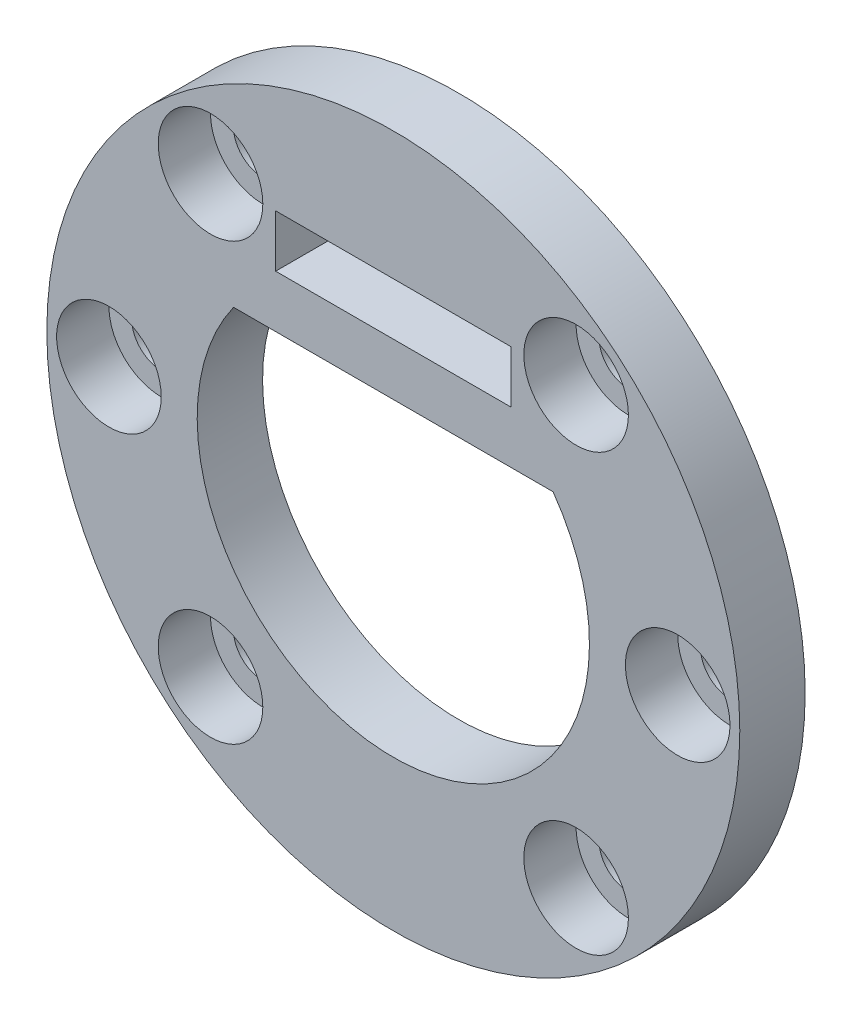
SolidWorks part; units mm, degrees
ref_plane "前视基准面" through (0, 0, 0) normal (0, 0, 1) x (1, 0, 0)
ref_plane "上视基准面" through (0, 0, 0) normal (0, 1, 0) x (1, 0, 0)
ref_plane "右视基准面" through (0, 0, 0) normal (1, 0, 0) x (0, 0, -1)
sketch "草图1" plane through (0, 0, 0) normal (0, 0, 1) x (1, 0, 0)
  circle A3 centre (0, 0) radius 26.5
extrude "凸台-拉伸1" add sketch "草图1" along normal blind 5
hole_wizard "M4 六角凹头盖的柱孔1" positions "3D草图2" profile "草图3" counterbore size "M4" standard "BSI" end condition through all
sketch3d "3D草图2"
  point P14 (-13.9806, 16.6615, 0)
  point P34 (-13.9806, 16.6615, 5)
  point P36 (13.9806, 16.6615, 5)
  point P38 (-21.75, 0, 5)
  point P40 (-13.9806, -16.6615, 5)
  point P42 (13.9806, -16.6615, 5)
  point P44 (21.75, 0, 5)
sketch "草图3" plane through (21.75, 0, 5) normal (1, 0, 0) x (0, -1, 0)
  line L0 (0, 0) -> (0, 5)
  line L1 (0, 5) -> (2.25, 5)
  line L3 (2.25, 5) -> (2.25, 4)
  line L4 (2.25, 4) -> (4, 4)
  line L5 (4, 4) -> (4, 0)
  line L7 (4, 0) -> (0, 0)
  line L11 (0, -6.35) -> (0, 107.95) construction
  dimension "通孔孔直径" = 4.5
  dimension "通孔孔深度" = 5
  dimension "柱形沉头孔直径" = 8
  dimension "柱形沉头孔深度" = 4
ref_plane "基准面1" through (0, 0, 5) normal (0, 0, 1) x (1, 0, 0)
sketch "参考" plane through (0, 0, 5) normal (0, 0, 1) x (1, 0, 0)
  line L12 (-20.7304, 8.7) -> (19.3146, 8.7) construction
ref_plane "基准面3" through (0, 8.7, 0) normal (0, -1, 0) x (1, 0, 0)
sketch "草图5" plane through (0, 8.7, 0) normal (0, -1, 0) x (1, 0, 0)
  line L0 (-26.5, 5) -> (-26.5, 14.9781)
  line L4 (26.5, 5) -> (26.5, 14.9781)
  line L9 (-26.5, 5) -> (26.5, 5)
  arc A4 (26.5, 14.9781) -> (-26.5, 14.9781) centre (0, 55) ccw
extrude "盘面" add sketch "草图5" against normal blind 8
sketch "草图6" plane through (0, 0, 5) normal (0, 0, 1) x (1, 0, 0)
  circle A0 centre (-13.9806, 16.6615) radius 4
  circle A1 centre (13.9806, 16.6615) radius 4
extrude "螺孔" cut sketch "草图6" along normal blind 22
sketch "草图8" plane through (0, 8.7, 0) normal (0, -1, 0) x (1, 0, 0)
  circle A1 centre (0, 55) radius 34.5
extrude "盘面切割" cut sketch "草图8" against normal through all
hole_wizard "M3 六角凹头盖的柱孔1" positions "3D草图3" profile "草图10" counterbore size "M3" standard "BSI" end condition through all
sketch3d "3D草图3"
  line L0 (0, 16.7, 55) -> (0, 8.7, 55) construction
  line L5 (0, 16.7, 55) -> (9.5763, 16.7, 19.2607)
  line L7 (0, 16.7, 55) -> (-9.5763, 16.7, 90.7393)
  line L11 (26.163, 16.7, 28.837) -> (0, 16.7, 55)
  line L17 (35.7393, 16.7, 45.4237) -> (0, 16.7, 55)
  line L19 (0, 16.7, 55) -> (35.7393, 16.7, 64.5763)
  line L21 (0, 16.7, 55) -> (26.6194, 16.7, 81.6194)
  line L22 (0, 16.7, 55) -> (-26.163, 16.7, 28.837)
  line L37 (0, 16.7, 55) -> (9.5763, 16.7, 90.7393)
  line L44 (-9.5763, 16.7, 19.2607) -> (0, 16.7, 55)
  line L54 (0, 16.7, 55) -> (-35.7393, 16.7, 45.4237)
  line L56 (0, 16.7, 55) -> (-26.163, 16.7, 81.163)
  line L68 (0, 16.7, 55) -> (-35.7393, 16.7, 64.5763)
  point P19 (9.5763, 16.7, 19.2607)
  point P34 (26.163, 16.7, 28.837)
  point P43 (35.7393, 16.7, 45.4237)
  point P46 (35.7393, 16.7, 64.5763)
  point P49 (26.6194, 16.7, 81.6194)
  point P169 (9.5763, 16.7, 90.7393)
  point P171 (-9.5763, 16.7, 90.7393)
  point P173 (-26.163, 16.7, 81.163)
  point P181 (-26.163, 16.7, 28.837)
  point P183 (-35.7393, 16.7, 45.4237)
  point P185 (-35.7393, 16.7, 64.5763)
  point P187 (-9.5763, 16.7, 19.2607)
sketch "草图10" plane through (-9.5763, 16.7, 19.2607) normal (1, 0, 0) x (0, 0, 1)
  line L0 (0, 0) -> (0, 43.2)
  line L1 (0, 43.2) -> (1.7, 43.2)
  line L3 (1.7, 43.2) -> (1.7, 3)
  line L4 (1.7, 3) -> (3.25, 3)
  line L5 (3.25, 3) -> (3.25, 0)
  line L7 (3.25, 0) -> (0, 0)
  line L11 (0, -6.35) -> (0, 107.95) construction
  dimension "通孔孔直径" = 3.4
  dimension "通孔孔深度" = 43.2
  dimension "柱形沉头孔直径" = 6.5
  dimension "柱形沉头孔深度" = 3
sketch "草图11" plane through (0, 0, 0) normal (0, 0, 1) x (1, 0, 0)
  line L0 (-25.0312, 8.7) -> (-29.0312, 8.7)
  line L1 (-19.36, 8.7) -> (19.36, 8.7) construction
  line L2 (-29.0312, 8.7) -> (-29.0312, 16.7)
  line L3 (48, 16.7) -> (-48, 16.7) construction
  line L4 (-29.0312, 16.7) -> (-20.5757, 16.7)
  line L6 (29.0312, 16.7) -> (20.5757, 16.7)
  line L7 (29.0312, 8.7) -> (29.0312, 16.7)
  line L8 (25.0312, 8.7) -> (29.0312, 8.7)
  arc A0 (-25.0312, 8.7) -> (25.0312, 8.7) centre (0, 0) ccw construction
  arc A1 (-25.0312, 8.7) -> (-20.5757, 16.7) centre (0, 0) cw
  arc A2 (25.0312, 8.7) -> (20.5757, 16.7) centre (0, 0) ccw
extrude "切除-拉伸1" cut sketch "草图11" along normal blind 15
sketch "草图12" plane through (0, 8.7, 0) normal (0, -1, 0) x (1, 0, 0)
  line L2 (39.2995, 79.0331) -> (30.6404, 73.9927)
  line L3 (40.2995, 32.8878) -> (31.6288, 37.8938)
  line L5 (25.4094, 16.6939) -> (19.8988, 25.0014)
  line L6 (39.2995, 31.1557) -> (30.6288, 36.1618)
  line L7 (31.6038, 72.2393) -> (40.2207, 77.2552)
  line L9 (-1, 96.0328) -> (-1, 90.9861)
  line L10 (1, 96.0328) -> (1, 101.0547)
  line L11 (1, 96.0328) -> (1, 90.9861)
  line L12 (-1, 96.0328) -> (-1, 101.0547)
  line L13 (-31.6038, 72.2393) -> (-40.2207, 77.2552)
  line L14 (-39.2995, 31.1557) -> (-30.6288, 36.1618)
  line L15 (-25.4094, 16.6939) -> (-19.8988, 25.0014)
  line L16 (-40.2995, 32.8878) -> (-31.6288, 37.8938)
  line L17 (-39.2995, 79.0331) -> (-30.6404, 73.9927)
  arc A9 (27.8489, 77.813) -> (22.813, 82.849) centre (26.6194, 81.6194) ccw
  arc A13 (12.9499, 88.5902) -> (5.5801, 90.5649) centre (9.5763, 90.7393) ccw
  arc A14 (33.5513, 42.0651) -> (35.5645, 49.4283) centre (35.7393, 45.4237) ccw
  arc A15 (35.5633, 60.5798) -> (33.59, 67.9502) centre (35.7393, 64.5763) ccw
  arc A16 (22.6075, 26.986) -> (27.9776, 32.4112) centre (26.163, 28.837) ccw
  arc A17 (12.9499, 88.5902) -> (22.813, 82.849) centre (0, 55) cw
  arc A18 (33.59, 67.9502) -> (31.6038, 72.2393) centre (0, 55) ccw
  arc A19 (35.5633, 60.5798) -> (35.5645, 49.4283) centre (0, 55) cw
  arc A20 (30.6288, 36.1618) -> (27.9776, 32.4112) centre (0, 55) cw
  arc A21 (22.6075, 26.986) -> (19.8988, 25.0014) centre (0, 55) cw
  arc A22 (5.5801, 90.5649) -> (1, 90.9861) centre (0, 55) ccw
  arc A23 (25.4094, 16.6939) -> (39.2995, 31.1557) centre (0, 55) ccw
  arc A24 (31.6288, 37.8938) -> (33.5513, 42.0651) centre (0, 55) ccw
  arc A25 (40.2995, 32.8878) -> (40.2207, 77.2552) centre (0, 55) ccw
  arc A26 (39.2995, 79.0331) -> (1, 101.0547) centre (0, 55) ccw
  arc A27 (30.6404, 73.9927) -> (27.8992, 77.8296) centre (0, 55) ccw
  arc A28 (-30.6404, 73.9927) -> (-27.8992, 77.8296) centre (0, 55) cw
  arc A29 (-39.2995, 79.0331) -> (-1, 101.0547) centre (0, 55) cw
  arc A30 (-40.2995, 32.8878) -> (-40.2207, 77.2552) centre (0, 55) cw
  arc A31 (-31.6288, 37.8938) -> (-33.5513, 42.0651) centre (0, 55) cw
  arc A32 (-25.4094, 16.6939) -> (-39.2995, 31.1557) centre (0, 55) cw
  arc A33 (-5.5801, 90.5649) -> (-1, 90.9861) centre (0, 55) cw
  arc A34 (-22.6075, 26.986) -> (-19.8988, 25.0014) centre (0, 55) ccw
  arc A35 (-30.6288, 36.1618) -> (-27.9776, 32.4112) centre (0, 55) ccw
  arc A36 (-35.5633, 60.5798) -> (-35.5645, 49.4283) centre (0, 55) ccw
  arc A37 (-33.59, 67.9502) -> (-31.6038, 72.2393) centre (0, 55) cw
  arc A38 (-12.9499, 88.5902) -> (-22.813, 82.849) centre (0, 55) ccw
  arc A39 (-22.6075, 26.986) -> (-27.9776, 32.4112) centre (-26.163, 28.837) cw
  arc A40 (-35.5633, 60.5798) -> (-33.59, 67.9502) centre (-35.7393, 64.5763) cw
  arc A41 (-33.5513, 42.0651) -> (-35.5645, 49.4283) centre (-35.7393, 45.4237) cw
  arc A42 (-12.9499, 88.5902) -> (-5.5801, 90.5649) centre (-9.5763, 90.7393) cw
  arc A43 (-27.8489, 77.813) -> (-22.813, 82.849) centre (-26.6194, 81.6194) cw
extrude "切除-拉伸2" cut sketch "草图12" against normal blind 5 contours A27 L2 A26 L10 L11 A22 A13 A17 A9 | L3 A25 L7 A18 A15 A19 A14 A24 | L5 A23 L6 A20 A16 A21 | A28 A43 A38 A42 A33 L9 L12 A29 L17 | A31 A41 A36 A40 A37 L13 A30 L16 | A34 A39 A35 L14 A32 L15 region at (19.8462, 8.7, 89.8632) region at (40.0107, 8.7, 55.079) region at (30.014, 8.7, 26.342) region at (-19.8462, 8.7, 89.8632) region at (-40.0107, 8.7, 55.079) region at (-30.014, 8.7, 26.342)
sketch "草图13" plane through (0, 0, 5) normal (0, 0, 1) x (1, 0, 0)
  line L0 (-20.7304, 8.7) -> (19.3146, 8.7) construction
  line L1 (-12.2192, 8.7) -> (12.2192, 8.7)
  arc A1 (-12.2192, 8.7) -> (12.2192, 8.7) centre (0, 0) ccw
extrude "切除-拉伸3" cut sketch "草图13" against normal blind 10
sketch "草图15" plane through (0, 0, 5) normal (0, 0, 1) x (1, 0, 0)
  line L0 (48, 16.7) -> (-48, 16.7)
  line L1 (48, 16.7) -> (-48, 16.7) construction
  line L2 (-48, 16.7) -> (-48, 8.7)
  line L3 (-48, 8.7) -> (48, 8.7)
  line L4 (48, 8.7) -> (48, 16.7)
extrude "切除-拉伸4" cut sketch "草图15" along normal through all
sketch "草图17" plane through (0, 0, 5) normal (0, 0, 1) x (1, 0, 0)
  line L0 (0, 12.7) -> (-9, 12.7)
  line L9 (-9, 12.7) -> (-9, 16.7)
  line L10 (-9, 16.7) -> (9, 16.7)
  line L11 (9, 16.7) -> (9, 12.7)
  line L12 (9, 12.7) -> (0, 12.7)
extrude "切除-拉伸5" cut sketch "草图17" against normal blind 10
